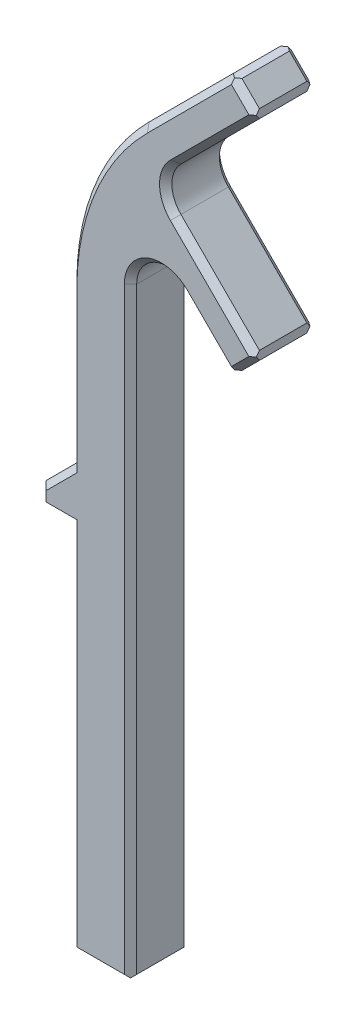
SolidWorks part; units mm, degrees
ref_plane "Front Plane" through (0, 0, 0) normal (0, 0, 1) x (1, 0, 0)
ref_plane "Top Plane" through (0, 0, 0) normal (0, 1, 0) x (1, 0, 0)
ref_plane "Right Plane" through (0, 0, 0) normal (1, 0, 0) x (0, 0, -1)
sketch "Sketch1" plane through (0, 0, 0) normal (0, 0, 1) x (1, 0, 0)
  line L0 (4.85, 55) -> (21.2132, 38.6368)
  line L1 (-4.85, -55) -> (4.85, -55)
  line L2 (-4.85, -55) -> (-4.85, 55)
  line L3 (-4.85, 55) -> (4.85, 55) construction
  line L4 (4.85, -55) -> (4.85, 55)
  line L5 (-4.85, -55) -> (4.85, 55) construction
  line L6 (-4.85, 55) -> (4.85, -55) construction
  line L7 (21.2132, 38.6368) -> (25.4558, 42.8794)
  line L8 (25.4558, 42.8794) -> (8.4853, 59.85)
  line L9 (8.4853, 59.85) -> (25.4558, 76.8206)
  line L10 (25.4558, 76.8206) -> (21.2132, 81.0632)
  line L11 (21.2132, 81.0632) -> (-4.85, 55)
  line L12 (8.4853, 59.85) -> (25.4558, 59.85) construction
  line L13 (25.4558, 76.8206) -> (25.4558, 59.85) construction
  line L14 (25.4558, 59.85) -> (25.4558, 42.8794) construction
  point P0 (0, 0)
  dimension "D1" = 9.7
  dimension "D2" = 6
  dimension "D3" = 24
  dimension "D4" = 110
extrude "Boss-Extrude1" add sketch "Sketch1" along normal mid plane 9.7
fillet "Fillet1" radius 5 1 edges at (4.85, 55, 0)
fillet "Fillet2" radius 40 1 edges at (-4.85, 55, 0)
fillet "Fillet3" radius 5 1 edges at (8.4853, 59.85, 0)
chamfer "Chamfer1" distance 1 angle 45 4 edges at (21.2132, 38.6368, 0) (25.4558, 42.8794, 0) (21.2132, 81.0632, 0) (25.4558, 76.8206, 0)
chamfer "Chamfer2" distance 1 angle 45 22 edges at (-4.85, -8.2843, -4.85) (-1.8052, 53.7388, -4.85) (13.6859, 73.5359, -4.85) (23.3345, 78.9419, -4.85) (23.3345, 78.9419, 4.85) (13.6859, 73.5359, 4.85) (-4.85, -8.2843, 4.85) (-1.8052, 53.7388, 4.85) (18.3848, 69.7495, 4.85) (10.5563, 59.85, 4.85) (18.3848, 49.9505, 4.85) (18.3848, 69.7495, -4.85) (10.5563, 59.85, -4.85) (18.3848, 49.9505, -4.85) (23.3345, 40.7581, -4.85) (23.3345, 40.7581, 4.85) (16.9458, 42.9042, -4.85) (7.9366, 47.5483, -4.85) (4.85, -6.0355, -4.85) (16.9458, 42.9042, 4.85) (7.9366, 47.5483, 4.85) (4.85, -6.0355, 4.85)
chamfer "Chamfer3" distance 1 angle 45 4 edges at (4.85, -55, 0) (0, -55, 4.85) (-4.85, -55, 0) (0, -55, -4.85)
sketch "Sketch2" plane through (0, 0, 4.85) normal (0, 0, 1) x (1, 0, 0)
  line L0 (-3.85, 5) -> (-9.85, 5)
  line L1 (-3.85, 38.4315) -> (-3.85, -54) construction
  line L2 (-9.85, 5) -> (-9.85, 8)
  line L3 (-9.85, 8) -> (-3.85, 14)
  line L4 (-3.85, 14) -> (-3.85, 5)
  line L5 (3.85, -55) -> (-3.85, -55) construction
  line L6 (-4.85, -54) -> (-4.85, 38.4315) construction
  point P8 (-4, 21.2011)
  point P9 (-14.5868, 9.5383)
  dimension "D1" = 60
  dimension "D2" = 3
  dimension "D3" = 5
  dimension "D4" = 45
extrude "Boss-Extrude2" add sketch "Sketch2" against normal up to surface (9.7 mm away) up to face at (10.7404, 37.5166, -4.85)
chamfer "Chamfer4" distance 1 angle 45 7 edges at (-6.85, 11, 4.85) (-9.85, 6.5, 4.85) (-6.85, 5, 4.85) (-6.85, 11, -4.85) (-9.85, 6.5, -4.85) (-6.85, 5, -4.85) (-9.85, 5, 0)
